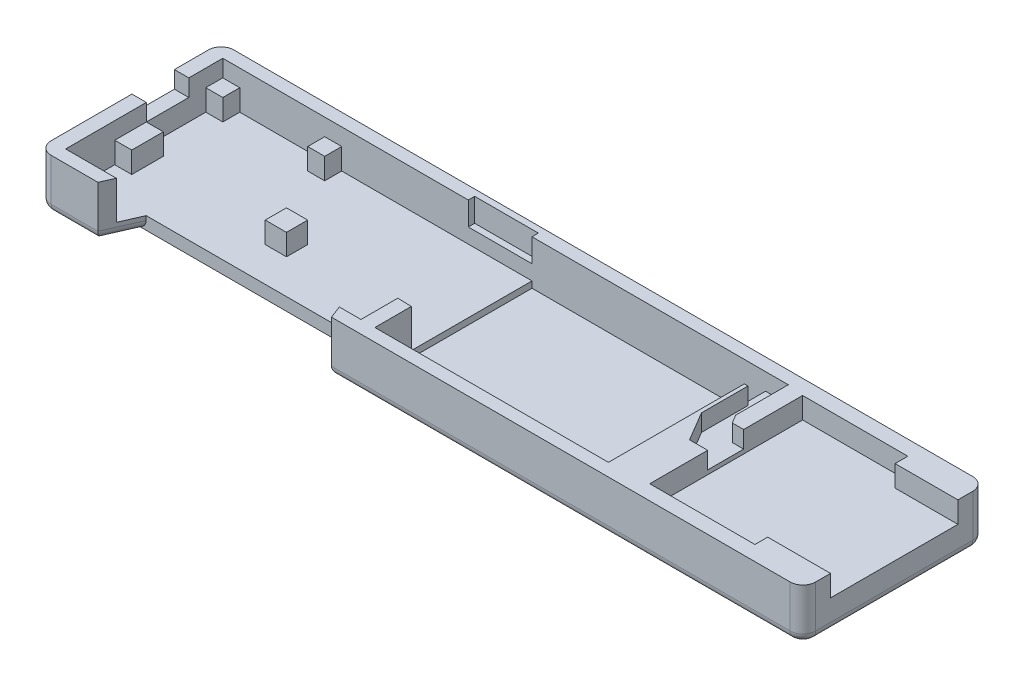
SolidWorks part; units mm, degrees
ref_plane "前视基准面" through (0, 0, 0) normal (0, 0, 1) x (1, 0, 0)
ref_plane "上视基准面" through (0, 0, 0) normal (0, 1, 0) x (1, 0, 0)
ref_plane "右视基准面" through (0, 0, 0) normal (1, 0, 0) x (0, 0, -1)
sketch "草图3" plane through (0, 0, 0) normal (0, 1, 0) x (1, 0, 0)
  line L1 (-39.9314, 29.2531) -> (140.0686, 29.2531)
  line L2 (-39.9314, 29.2531) -> (-39.9314, -13.7469)
  line L3 (-39.9314, -13.7469) -> (140.0686, -13.7469)
  line L4 (140.0686, 29.2531) -> (140.0686, -13.7469)
extrude "凸台-拉伸1" add sketch "草图3" along normal blind 12
sketch "草图4" plane through (0, 0, 0) normal (0, 1, 0) x (1, 0, 0)
  line L0 (-22.4696, -5.8589) -> (26.0023, -5.8589)
  line L1 (-39.9314, -13.7469) -> (140.0686, -13.7469) construction
  line L2 (-25.9314, -13.7469) -> (29.0686, -13.7469)
  line L5 (-25.9314, -13.7469) -> (-22.4696, -5.8589)
  line L6 (29.0686, -13.7469) -> (26.0023, -5.8589)
  point P11 (-22.4696, -5.8589)
  point P12 (26.0023, -5.8589)
extrude "切除-拉伸1" cut sketch "草图4" along normal blind 52
sketch "草图5" plane through (0, 12, 0) normal (0, 1, 0) x (1, 0, 0)
  line L6 (140.0686, -13.7469) -> (140.0686, 29.2531) construction
  line L7 (140.0686, 7.7531) -> (140.0686, 22.7531)
  line L8 (140.0686, 7.7531) -> (140.0686, -7.2469)
  line L9 (140.0686, 22.7531) -> (125.2765, 22.7531)
  line L10 (125.2765, 22.7531) -> (125.2765, -7.2469)
  line L11 (125.2765, -7.2469) -> (140.0686, -7.2469)
  point P0 (140.0686, 7.7531)
extrude "切除-拉伸2" cut sketch "草图5" against normal blind 5
sketch "草图7" plane through (0, 12, 0) normal (0, 1, 0) x (1, 0, 0)
  line L0 (125.2765, 22.7531) -> (125.2765, -7.2469) construction
  line L1 (125.2765, 7.7531) -> (125.2765, 25.7531)
  line L2 (125.2765, 7.7531) -> (125.2765, -10.2469)
  line L3 (125.2765, -10.2469) -> (100.5008, -10.2469)
  line L4 (100.5008, -10.2469) -> (100.5008, 25.7531)
  line L5 (100.5008, 25.7531) -> (125.2765, 25.7531)
  point P0 (125.2765, 7.7531)
extrude "切除-拉伸3" cut sketch "草图7" against normal blind 5
sketch "草图8" plane through (0, 12, 0) normal (0, 1, 0) x (1, 0, 0)
  line L1 (36.2763, 26.2531) -> (91.2763, 26.2531)
  line L2 (36.2763, 26.2531) -> (36.2763, -10.7469)
  line L3 (36.2763, -10.7469) -> (91.2763, -10.7469)
  line L4 (91.2763, 26.2531) -> (91.2763, -10.7469)
  line L6 (140.0686, 29.2531) -> (-39.9314, 29.2531) construction
  line L7 (29.0686, -13.7469) -> (140.0686, -13.7469) construction
  dimension "D1" = 3
  dimension "D2" = 3
extrude "切除-拉伸4" cut sketch "草图8" against normal blind 10.5
sketch "草图9" plane through (0, 12, 0) normal (0, 1, 0) x (1, 0, 0)
  line L0 (91.2763, -10.7469) -> (91.2763, 26.2531) construction
  line L1 (91.2763, 26.2531) -> (96.6358, 26.2531)
  line L2 (91.2763, 26.2531) -> (91.2763, 21.2551)
  line L4 (96.6358, 26.2531) -> (96.6358, 22.1306)
  line L5 (100.5008, 25.7531) -> (100.5008, -10.2469) construction
  line L7 (92.1327, 21.2551) -> (92.1327, 10.3104)
  line L12 (96.2367, 3.394) -> (100.5008, 3.394)
  line L13 (100.5008, 11.8772) -> (100.5008, 3.394)
  line L14 (92.1327, 10.3104) -> (96.2367, 3.394)
  line L15 (96.6358, 13.8621) -> (97.8136, 11.8772)
  line L17 (97.8136, 11.8772) -> (100.5008, 11.8772)
  line L19 (96.6358, 13.8621) -> (96.6358, 22.1306)
  line L20 (92.1327, 21.2551) -> (91.2763, 21.2551)
extrude "切除-拉伸5" cut sketch "草图9" against normal blind 4
sketch "草图10" plane through (0, 12, 0) normal (0, 1, 0) x (1, 0, 0)
  line L4 (-29.1302, -10.7469) -> (32.9986, -10.7469)
  line L5 (-29.1302, -10.7469) -> (-29.1302, -2.0631)
  line L6 (-29.1302, -2.0631) -> (32.9986, -2.0631)
  line L7 (32.9986, -10.7469) -> (32.9986, -2.0631)
extrude "切除-拉伸6" cut sketch "草图10" against normal blind 8
sketch "草图11" plane through (0, 12, 0) normal (0, 1, 0) x (1, 0, 0)
  line L0 (32.9986, -10.7469) -> (-36.5397, -10.7469)
  line L1 (36.2763, 26.2531) -> (36.2763, -10.7469) construction
  line L5 (-36.5397, 26.2531) -> (-36.5397, -10.7469)
  line L9 (36.2763, 26.2531) -> (36.2763, -2.1672)
  line L10 (-36.5397, 26.2531) -> (36.2763, 26.2531)
  line L11 (32.9986, -10.7469) -> (32.9986, -2.0631)
  line L12 (32.9986, -10.7469) -> (32.9986, -2.0631) construction
  line L13 (32.9986, -2.0631) -> (36.2763, -2.1672)
extrude "切除-拉伸8" cut sketch "草图11" against normal blind 9
fillet "圆角2" radius 2 7 edges at (140.0686, 0, -7.7531) (84.5686, 0, 13.7469) (27.5354, 0, 9.8029) (-24.2005, 0, 9.8029) (-32.9314, 0, 13.7469) (-39.9314, 0, -7.7531) (50.0686, 0, -29.2531)
fillet "圆角3" radius 3 8 edges at (-39.3456, 0.5858, -28.6673) (-39.3456, 0.5858, 13.1611) (139.4828, 0.5858, 13.1611) (139.4828, 0.5858, -28.6673) (140.0686, 7, -29.2531) (140.0686, 7, 13.7469) (-39.9314, 7, 13.7469) (-39.9314, 7, -29.2531)
sketch "草图12" plane through (-36.5397, 0, 0) normal (1, 0, 0) x (0, 0, -1)
  line L5 (8.2531, 12) -> (18.2531, 12)
  line L6 (8.2531, 12) -> (8.2531, 8)
  line L7 (8.2531, 8) -> (18.2531, 8)
  line L8 (18.2531, 12) -> (18.2531, 8)
  line L9 (26.2531, 3) -> (26.2531, 12) construction
  dimension "D1" = 10
  dimension "D2" = 8
  dimension "D3" = 4
extrude "切除-拉伸9" cut sketch "草图12" against normal blind 10
sketch "草图13" plane through (0, 3, 0) normal (0, 1, 0) x (1, 0, 0)
  line L0 (-36.5397, 26.2531) -> (-36.5397, -10.7469) construction
  line L1 (-36.5397, 22.2531) -> (-32.5397, 22.2531)
  line L2 (-36.5397, 22.2531) -> (-36.5397, 26.2531)
  line L3 (-36.5397, 26.2531) -> (-32.5397, 26.2531)
  line L4 (-32.5397, 22.2531) -> (-32.5397, 26.2531)
  line L5 (36.2763, 26.2531) -> (-36.5397, 26.2531) construction
  line L7 (-36.5397, 8.2531) -> (-32.5397, 8.2531)
  line L8 (-36.5397, 8.2531) -> (-36.5397, 0.8178)
  line L9 (-36.5397, 0.8178) -> (-32.5397, 0.8178)
  line L10 (-32.5397, 8.2531) -> (-32.5397, 0.8178)
  line L11 (-12.5397, 26.2531) -> (-8.5397, 26.2531)
  line L12 (-12.5397, 26.2531) -> (-12.5397, 22.2531)
  line L13 (-12.5397, 22.2531) -> (-8.5397, 22.2531)
  line L14 (-8.5397, 26.2531) -> (-8.5397, 22.2531)
  line L15 (-36.5397, 8.2531) -> (-36.5397, -10.7469) construction
  line L16 (-2.5397, 7.2531) -> (2.4603, 7.2531)
  line L17 (-2.5397, 7.2531) -> (-2.5397, 2.2531)
  line L18 (-2.5397, 2.2531) -> (2.4603, 2.2531)
  line L19 (2.4603, 7.2531) -> (2.4603, 2.2531)
  line L20 (96.6358, 26.2531) -> (-36.5397, 26.2531) construction
  point P16 (-12.5397, 24.2531)
  dimension "D1" = 14
  dimension "D2" = 4
  dimension "D3" = 4
  dimension "D4" = 4
  dimension "D5" = 24
  dimension "D6" = 4
  dimension "D7" = 4
  dimension "D8" = 34
  dimension "D9" = 5
  dimension "D10" = 5
  dimension "D11" = 19
extrude "凸台-拉伸2" add sketch "草图13" along normal blind 5
sketch "草图14" plane through (0, 12, 0) normal (0, 1, 0) x (1, 0, 0)
  line L0 (96.6358, 26.2531) -> (-36.5397, 26.2531) construction
  line L1 (36.2763, 26.2531) -> (21.2763, 26.2531)
  line L2 (36.2763, 26.2531) -> (36.2763, 27.7531)
  line L3 (36.2763, 27.7531) -> (21.2763, 27.7531)
  line L4 (21.2763, 26.2531) -> (21.2763, 27.7531)
  line L5 (91.2763, 26.2531) -> (36.2763, 26.2531) construction
  dimension "D1" = 15
extrude "切除-拉伸10" cut sketch "草图14" against normal blind 5.5
